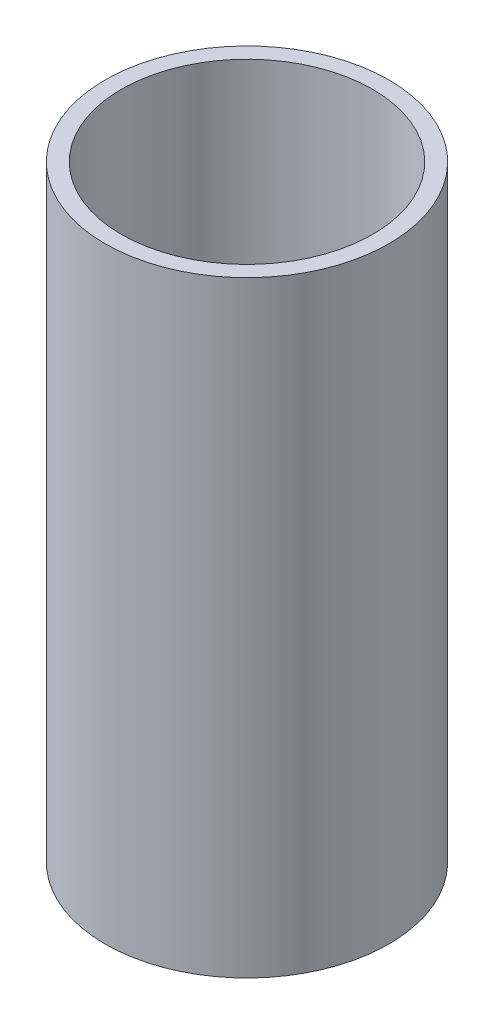
SolidWorks part; units mm, degrees
ref_plane "Front Plane" through (0, 0, 0) normal (0, 0, 1) x (1, 0, 0)
ref_plane "Top Plane" through (0, 0, 0) normal (0, 1, 0) x (1, 0, 0)
ref_plane "Right Plane" through (0, 0, 0) normal (1, 0, 0) x (0, 0, -1)
sketch "Sketch1" plane through (0, 0, 0) normal (0, 1, 0) x (1, 0, 0)
  circle A0 centre (0, 0) radius 30
  dimension "SLEEVE_OD" = 60
extrude "Boss-Extrude1" add sketch "Sketch1" along normal blind 128.2356
sketch "Sketch2" plane through (0, 0, 0) normal (0, 1, 0) x (1, 0, 0)
  circle A0 centre (0, 0) radius 26.5741
  dimension "BORE_D" = 53.1483
extrude "Cut-Extrude1" cut sketch "Sketch2" along normal through all
chamfer "Chamfer1" distance 3.5252 angle 24.061 rebuild error yes
